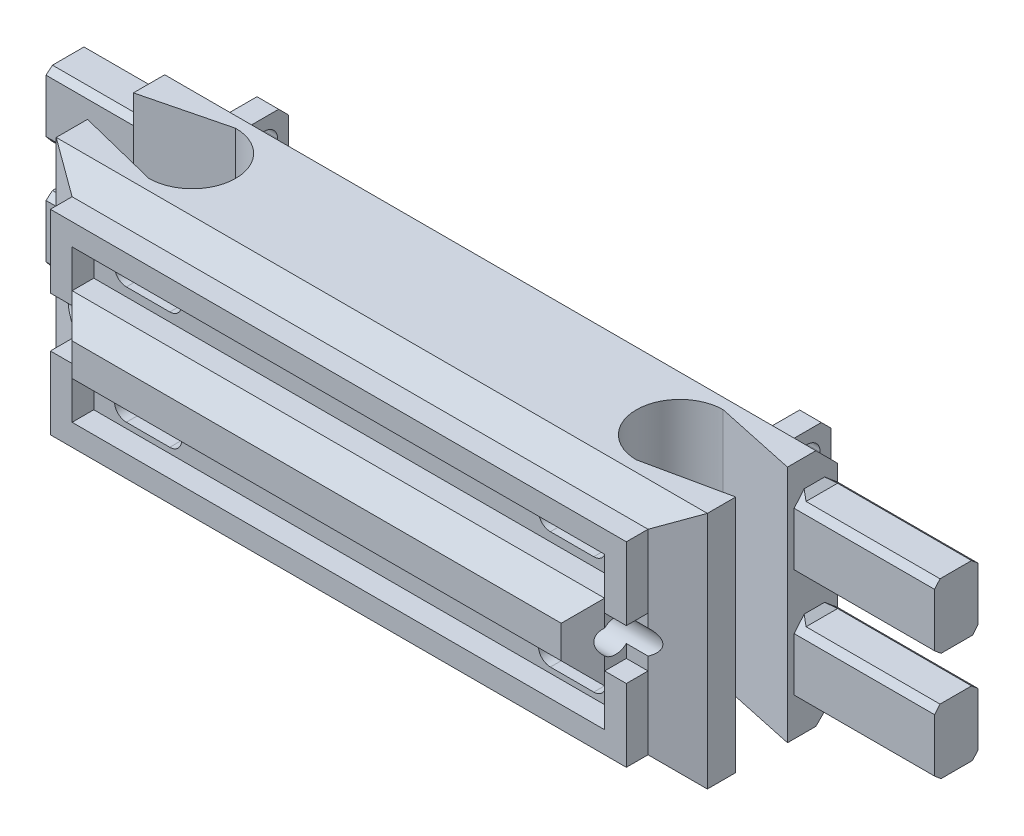
SolidWorks part; units mm, degrees
ref_plane "Front Plane" through (0, 0, 0) normal (0, 0, 1) x (1, 0, 0)
ref_plane "Top Plane" through (0, 0, 0) normal (0, 1, 0) x (1, 0, 0)
ref_plane "Right Plane" through (0, 0, 0) normal (1, 0, 0) x (0, 0, -1)
sketch "Base" plane through (0, 0, 0) normal (0, 0, 1) x (1, 0, 0)
  line L1 (0, 0) -> (30, 0)
  line L2 (0, 0) -> (0, 11)
  line L3 (0, 11) -> (30, 11)
  line L4 (30, 0) -> (30, 11)
  dimension "D1" = 30
  dimension "D2" = 11
extrude "Boss-Extrude1" add sketch "Base" along normal blind 7
chamfer "Chamfer4" distance 1 angle 45 2 edges at (15, 11, 7) (15, 0, 7)
chamfer "Chamfer5" distance 1 angle 60 2 edges at (0, 5.5, 7) (30, 5.5, 7)
chamfer "Chamfer6" distance 1 angle 45 2 edges at (15, 11, 0) (15, 0, 0)
sketch "Tendon extrude" plane through (0, 0, 0) normal (0, -1, 0) x (1, 0, 0)
  line L0 (15, 6) -> (15, -3.9632) construction
  line L1 (30, 6) -> (0, 6) construction
  line L2 (0, 3.5) -> (21.7648, 3.5) construction
  line L3 (0, 6) -> (0, 1) construction
  line L4 (3.77, 3.5) -> (-2.23, 3.5) construction
  line L5 (-2.23, 3) -> (-2.23, 4)
  line L6 (3.77, 5.5) -> (-2.23, 4)
  line L7 (-2.23, 3) -> (3.77, 1.5)
  line L10 (26.23, 3.5) -> (33.23, 3.5) construction
  line L11 (33.23, 3) -> (33.23, 4)
  line L12 (26.23, 5.5) -> (33.23, 4)
  line L13 (33.23, 3) -> (26.23, 1.5)
  circle A0 centre (3.77, 3.5) radius 2
  circle A1 centre (26.23, 3.5) radius 2
  dimension "D1" = 4
  dimension "D2" = 3.77
  dimension "D3" = 1
  dimension "D4" = 6
  dimension "D5" = 1
  dimension "D6" = 7
sketch "Sketch8" plane through (0, 0, 7) normal (0, 0, 1) x (1, 0, 0)
  line L0 (28.2679, 5.5) -> (1.7321, 5.5) construction
  line L1 (28.2679, 1) -> (28.2679, 10) construction
  line L2 (1.7321, 10) -> (1.7321, 1) construction
  line L3 (15, 1) -> (15, 10) construction
  line L4 (1.7321, 1) -> (28.2679, 1) construction
  line L5 (28.2679, 10) -> (1.7321, 10) construction
  line L6 (2.7321, 3.75) -> (2.7321, 7.25)
  line L7 (27.2679, 7.25) -> (2.7321, 7.25)
  line L8 (27.2679, 7.25) -> (27.2679, 3.75)
  line L9 (27.2679, 3.75) -> (2.7321, 3.75)
  point P17 (2.7321, 5.5)
  point P18 (27.2679, 5.5)
  dimension "D1" = 1.75
  dimension "D2" = 1
  dimension "D3" = 1
extrude "Boss-Extrude5" add sketch "Sketch8" along normal blind 2
sketch "Sketch9" plane through (27.2679, 0, 0) normal (1, 0, 0) x (0, 0, -1)
  line L0 (-9, 5.5) -> (-7, 5.5) construction
  line L1 (-9, 3.75) -> (-9, 7.25) construction
  line L2 (-7, 3.75) -> (-7, 7.25) construction
  circle A0 centre (-7.5, 5.5) radius 0.75
  dimension "D1" = 1.5
  dimension "D2" = 1.5
extrude "Cut-Extrude5" cut sketch "Sketch9" against normal blind 34.5 and the other way blind 4.2544
chamfer "Chamfer9" distance 1 angle 45 4 edges at (2.7321, 5.5, 9) (15, 7.25, 9) (27.2679, 5.5, 9) (15, 3.75, 9)
sketch "Sketch13" plane through (0, 0, 0) normal (0, 0, -1) x (-1, 0, 0)
  line L0 (0, 5.5) -> (-33.4926, 5.5) construction
  line L1 (0, 10) -> (0, 1) construction
  line L2 (-15, 1) -> (-15, 15.915) construction
  line L3 (-30, 1) -> (0, 1) construction
  line L4 (-1, 7.25) -> (-10, 7.25)
  line L5 (-20, 7.25) -> (-20, 3.75)
  line L6 (-1, 7.25) -> (-1, 3.75)
  line L7 (-1, 3.75) -> (-10, 3.75)
  line L8 (-10, 7.25) -> (-10, 3.75)
  line L9 (-29, 7.25) -> (-20, 7.25)
  line L10 (-29, 3.75) -> (-20, 3.75)
  line L11 (-29, 7.25) -> (-29, 3.75)
  point P13 (-10, 5.5)
  point P14 (-1, 5.5)
  dimension "D1" = 1.75
  dimension "D2" = 1
  dimension "D3" = 5
extrude "Boss-Extrude6" add sketch "Sketch13" along normal blind 2
chamfer "Chamfer10" distance 1 angle 45 8 edges at (20, 5.5, -2) (24.5, 3.75, -2) (29, 5.5, -2) (24.5, 7.25, -2) (5.5, 7.25, -2) (1, 5.5, -2) (5.5, 3.75, -2) (10, 5.5, -2)
sketch "Sketch14" plane through (1, 0, 0) normal (-1, 0, 0) x (0, 0, 1)
  line L0 (-1, 5.5) -> (0, 5.5) construction
  line L1 (-1, 7.25) -> (-1, 3.75) construction
  line L2 (0, 3.75) -> (0, 7.25) construction
  line L3 (-2, 4.75) -> (-2, 6.25) construction
  circle A0 centre (-0.5, 5.5) radius 0.75
  dimension "D1" = 1.5
  dimension "D2" = 1.5
extrude "Cut-Extrude6" cut sketch "Sketch14" against normal blind 30 and the other way blind 3
sketch "Sketch15" plane through (0, 0, 0) normal (0, 0, -1) x (-1, 0, 0)
  line L0 (-28, 4.75) -> (-21, 4.75) construction
  line L1 (-28, 1) -> (-27, 1)
  line L2 (-28, 1) -> (-28, 4.75)
  line L3 (-28, 4.75) -> (-27, 4.75)
  line L4 (-27, 1) -> (-27, 4.75)
  line L5 (-28, 6.25) -> (-28, 4.75) construction
  line L6 (-15, 1) -> (-15, 10) construction
  line L7 (-30, 1) -> (0, 1) construction
  line L8 (0, 10) -> (-30, 10) construction
  line L9 (-21, 6.25) -> (-28, 6.25) construction
  line L10 (-28, 6.25) -> (-27, 6.25)
  line L11 (-28, 6.25) -> (-28, 10)
  line L12 (-28, 10) -> (-27, 10)
  line L13 (-27, 6.25) -> (-27, 10)
  line L14 (-2, 1) -> (-3, 1)
  line L15 (-2, 1) -> (-2, 4.75)
  line L16 (-3, 1) -> (-3, 4.75)
  line L17 (-2, 4.75) -> (-3, 4.75)
  line L18 (-2, 6.25) -> (-3, 6.25)
  line L19 (-2, 10) -> (-3, 10)
  line L20 (-3, 6.25) -> (-3, 10)
  line L21 (-2, 6.25) -> (-2, 10)
  dimension "D1" = 0
  dimension "D3" = 1
  dimension "D4" = 0
  dimension "D5" = 0
extrude "Boss-Extrude7" add sketch "Sketch15" along normal blind 2
sketch "Sketch16" plane through (28, 0, 0) normal (1, 0, 0) x (0, 0, -1)
  line L0 (0.6, 3.15) -> (0.6, 2.15) construction
  line L1 (1.2, 3.15) -> (1.2, 2.15)
  line L2 (0, 3.15) -> (0, 2.15)
  line L3 (1, 3.75) -> (0, 3.75) construction
  line L5 (0.6, 7.85) -> (0.6, 8.85) construction
  line L6 (0, 7.85) -> (0, 8.85)
  line L7 (1.2, 7.85) -> (1.2, 8.85)
  line L9 (1, 7.25) -> (0, 7.25) construction
  line L10 (0, 3.75) -> (0, 1) construction
  arc A0 (1.2, 3.15) -> (0, 3.15) centre (0.6, 3.15) ccw
  arc A1 (0, 2.15) -> (1.2, 2.15) centre (0.6, 2.15) ccw
  arc A2 (0, 7.85) -> (1.2, 7.85) centre (0.6, 7.85) ccw
  arc A3 (1.2, 8.85) -> (0, 8.85) centre (0.6, 8.85) ccw
  point P2 (0.6, 2.65)
  point P13 (0.6, 8.35)
  point P20 (0.5, 7.25)
  dimension "D1" = 1
  dimension "D2" = 0.6
  dimension "D3" = 0.6
  dimension "D4" = 0
  dimension "D5" = 0.6
extrude "Cut-Extrude7" cut sketch "Sketch16" against normal blind 26
chamfer "Chamfer11" distance 0.3 angle 45 8 edges at (2, 2.875, -2) (3, 2.875, -2) (3, 8.125, -2) (2, 8.125, -2) (28, 8.125, -2) (27, 8.125, -2) (28, 2.875, -2) (27, 2.875, -2)
chamfer "Chamfer12" distance 0.75 angle 45 4 edges at (27.5, 1, -2) (27.5, 10, -2) (2.5, 10, -2) (2.5, 1, -2)
extrude "Cut-Extrude8" cut sketch "Tendon extrude" against normal up to surface (11 mm away)
sketch "Sketch18" plane through (30, 0, 0) normal (1, 0, 0) x (0, 0, -1)
  line L0 (-2.3079, 5.5) -> (-0.25, 5.5) construction
  line L1 (-2.3079, 11) -> (-2.3079, 0) construction
  line L3 (-2, 6.5) -> (0, 6.5)
  line L4 (-2, 6.5) -> (-2, 9.5)
  line L5 (-2, 9.5) -> (0, 9.5)
  line L6 (0, 6.5) -> (0, 9.5)
  line L7 (-2, 4.5) -> (0, 4.5)
  line L8 (0, 4.5) -> (0, 1.5)
  line L9 (-2, 1.5) -> (0, 1.5)
  line L10 (-2, 4.5) -> (-2, 1.5)
  line L11 (0, 6.059) -> (0, 10) construction
  arc A0 (0, 6.059) -> (0, 4.941) centre (0.5, 5.5) ccw construction
  dimension "D1" = 3
  dimension "D2" = 2
  dimension "D3" = 1
extrude "Boss-Extrude8" add sketch "Sketch18" along normal blind 6.47
chamfer "Chamfer13" distance 0.25 angle 50 8 edges at (33.235, 1.5, 2) (33.235, 4.5, 2) (33.235, 6.5, 2) (33.235, 9.5, 2) (33.235, 9.5, 0) (33.235, 6.5, 0) (33.235, 4.5, 0) (33.235, 1.5, 0)
chamfer "Chamfer14" distance 0.25 angle 50 4 edges at (30, 9.5, 1.024) (30, 1.5, 0.976) (30, 4.5, 1.024) (30, 6.5, 0.976)
sketch "Sketch19" plane through (0, 0, 0) normal (-1, 0, 0) x (0, 0, 1)
  line L0 (0.25, 5.5) -> (2.4425, 5.5) construction
  line L1 (2.4425, 11) -> (2.4425, 0) construction
  line L3 (0, 4.5) -> (2, 4.5)
  line L4 (0, 4.5) -> (0, 1.5)
  line L5 (0, 1.5) -> (2, 1.5)
  line L6 (2, 4.5) -> (2, 1.5)
  line L7 (2, 6.5) -> (2, 9.5)
  line L8 (0, 9.5) -> (2, 9.5)
  line L9 (0, 6.5) -> (0, 9.5)
  line L10 (0, 6.5) -> (2, 6.5)
  line L11 (0, 4.941) -> (0, 1) construction
  arc A0 (0, 4.941) -> (0, 6.059) centre (-0.5, 5.5) ccw construction
  dimension "D1" = 2
  dimension "D2" = 3
  dimension "D4" = 1
extrude "Boss-Extrude9" add sketch "Sketch19" along normal blind 4.47
chamfer "Chamfer15" distance 0.25 angle 50 8 edges at (-2.235, 1.5, 2) (-2.235, 4.5, 2) (-2.235, 9.5, 2) (-2.235, 6.5, 2) (-2.235, 1.5, 0) (-2.235, 4.5, 0) (-2.235, 9.5, 0) (-2.235, 6.5, 0)
chamfer "Chamfer16" distance 0.25 angle 50 4 edges at (0, 9.5, 0.976) (0, 6.5, 1.024) (0, 4.5, 0.976) (0, 1.5, 1.024)
sketch "Sketch20" plane through (0, 0, 7) normal (0, 0, 1) x (1, 0, 0)
  line L0 (28.2679, 6.059) -> (28.2679, 10) construction
  line L1 (1.7321, 10) -> (28.2679, 10)
  line L2 (1.7321, 10) -> (1.7321, 9)
  line L3 (1.7321, 9) -> (28.2679, 9)
  line L4 (28.2679, 10) -> (28.2679, 9)
  line L5 (2.7321, 7.25) -> (2.7321, 6.059) construction
  line L6 (2.7321, 6.6545) -> (1.7321, 6.6545)
  line L7 (2.7321, 6.6545) -> (2.7321, 9)
  line L8 (2.7321, 9) -> (1.7321, 9)
  line L9 (1.7321, 6.6545) -> (1.7321, 9)
  line L10 (27.2679, 6.059) -> (27.2679, 7.25) construction
  line L11 (27.2679, 6.6545) -> (28.2679, 6.6545)
  line L12 (27.2679, 6.6545) -> (27.2679, 9)
  line L13 (27.2679, 9) -> (28.2679, 9)
  line L14 (28.2679, 6.6545) -> (28.2679, 9)
  line L15 (1.7321, 4.941) -> (1.7321, 1) construction
  line L16 (28.2679, 1) -> (1.7321, 1)
  line L17 (28.2679, 1) -> (28.2679, 2)
  line L18 (28.2679, 2) -> (1.7321, 2)
  line L19 (1.7321, 1) -> (1.7321, 2)
  line L20 (2.7321, 4.941) -> (2.7321, 3.75) construction
  line L21 (2.7321, 4.3455) -> (1.7321, 4.3455)
  line L22 (2.7321, 4.3455) -> (2.7321, 2)
  line L23 (2.7321, 2) -> (1.7321, 2)
  line L24 (1.7321, 4.3455) -> (1.7321, 2)
  line L25 (27.2679, 3.75) -> (27.2679, 4.941) construction
  line L26 (28.2679, 2) -> (27.2679, 2)
  line L27 (28.2679, 2) -> (28.2679, 4.3455)
  line L28 (28.2679, 4.3455) -> (27.2679, 4.3455)
  line L29 (27.2679, 2) -> (27.2679, 4.3455)
  line M2 (28.2679, 6.059) -> (28.2679, 10)
  line M3 (28.2679, 10) -> (1.7321, 10)
  line M4 (1.7321, 10) -> (1.7321, 6.059)
  line M6 (2.7321, 6.059) -> (2.7321, 7.25)
  line M8 (27.2679, 7.25) -> (27.2679, 6.059)
extrude "Boss-Extrude10" add sketch "Sketch20" along normal blind 1 contours L7 L3 L6 M6 M4 | L3 M4 M2 M3 | L12 L11 L3 M8 M2 | L29 L18 L27 L28 | L19 L16 L17 L18 | L21 L24 L18 L22
sketch "Sketch21" plane through (0, 0, 7) normal (0, 0, 1) x (1, 0, 0)
  line L0 (4.2321, 8.2) -> (6.2321, 8.2) construction
  line L1 (4.2321, 8.7469) -> (6.2321, 8.7469)
  line L2 (4.2321, 7.6531) -> (6.2321, 7.6531)
  line L3 (23.7679, 8.2) -> (25.7679, 8.2) construction
  line L4 (23.7679, 8.7469) -> (25.7679, 8.7469)
  line L5 (23.7679, 7.6531) -> (25.7679, 7.6531)
  line L6 (23.7679, 2.8) -> (25.7679, 2.8) construction
  line L7 (23.7679, 3.3469) -> (25.7679, 3.3469)
  line L8 (23.7679, 2.2531) -> (25.7679, 2.2531)
  line L9 (6.2321, 2.8) -> (4.2321, 2.8) construction
  line L10 (6.2321, 2.2531) -> (4.2321, 2.2531)
  line L11 (6.2321, 3.3469) -> (4.2321, 3.3469)
  line L12 (2.7321, 9) -> (27.2679, 9) construction
  line L13 (27.2679, 2) -> (2.7321, 2) construction
  line L14 (2.7321, 7.25) -> (2.7321, 9) construction
  line L15 (27.2679, 7.25) -> (27.2679, 9) construction
  arc A0 (4.2321, 8.7469) -> (4.2321, 7.6531) centre (4.2321, 8.2) ccw
  arc A1 (6.2321, 7.6531) -> (6.2321, 8.7469) centre (6.2321, 8.2) ccw
  arc A2 (23.7679, 8.7469) -> (23.7679, 7.6531) centre (23.7679, 8.2) ccw
  arc A3 (25.7679, 7.6531) -> (25.7679, 8.7469) centre (25.7679, 8.2) ccw
  arc A4 (23.7679, 3.3469) -> (23.7679, 2.2531) centre (23.7679, 2.8) ccw
  arc A5 (25.7679, 2.2531) -> (25.7679, 3.3469) centre (25.7679, 2.8) ccw
  arc A6 (6.2321, 2.2531) -> (6.2321, 3.3469) centre (6.2321, 2.8) ccw
  arc A7 (4.2321, 3.3469) -> (4.2321, 2.2531) centre (4.2321, 2.8) ccw
  point P2 (5.2321, 8.2)
  point P7 (24.7679, 8.2)
  point P14 (24.7679, 2.8)
  point P21 (5.2321, 2.8)
  point P32 (2.7321, 8.125)
  point P35 (27.2679, 8.125)
  dimension "D1" = 0.8
  dimension "D2" = 0.8
  dimension "D3" = 2
  dimension "D4" = 1.5
  dimension "D5" = 1.5
extrude "Cut-Extrude9" cut sketch "Sketch21" against normal blind 1
